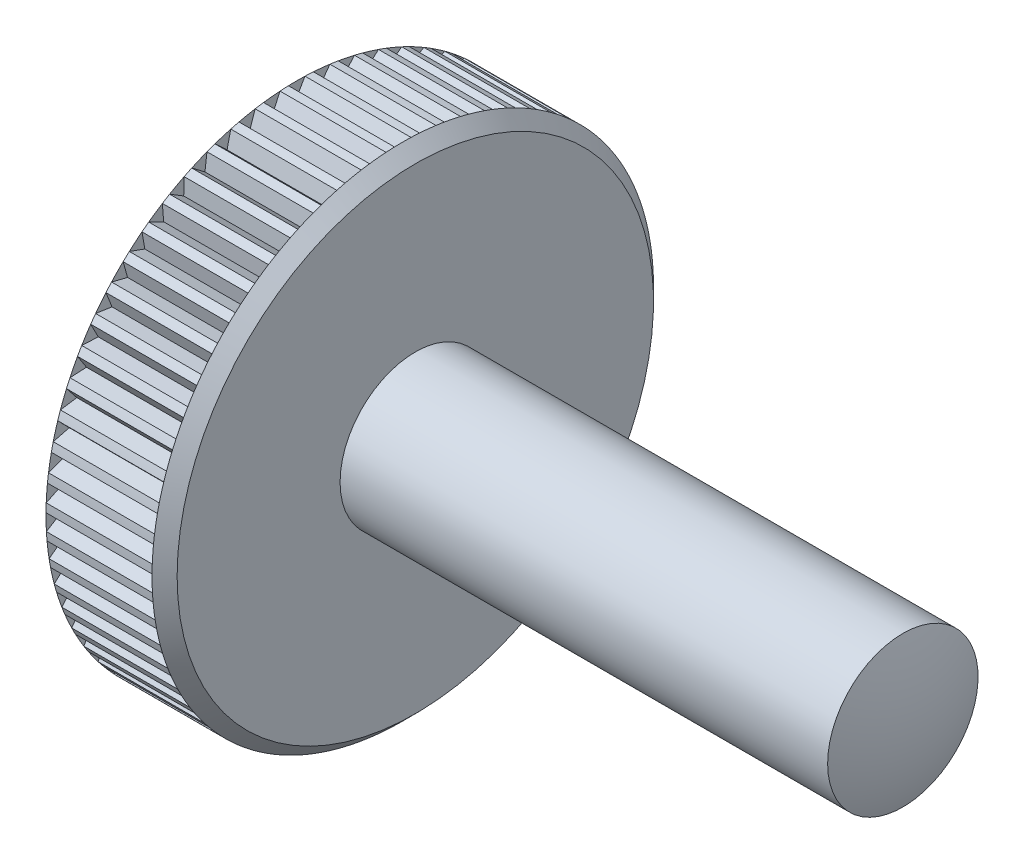
SolidWorks part; units mm, degrees
ref_plane "Front" through (0, 0, 0) normal (0, 0, 1) x (1, 0, 0)
ref_plane "Top" through (0, 0, 0) normal (0, 1, 0) x (1, 0, 0)
ref_plane "Right" through (0, 0, 0) normal (1, 0, 0) x (0, 0, -1)
sketch "Sketch1" plane through (0, 0, 0) normal (0, 0, 1) x (1, 0, 0)
  line L0 (0, 0) -> (26, 0)
  line L1 (1.2702, 10) -> (6, 10)
  line L2 (6, 10) -> (6, 3)
  line L7 (6, 3) -> (25.446, 3)
  line L9 (-48.2111, 0) -> (101.1311, 0) construction
  arc A0 (26, 0) -> (25.446, 3) centre (17.6, 0) ccw
  arc A1 (1.2702, 10) -> (0, 0) centre (40, 0) ccw
  dimension "l" = 20
  dimension "k" = 6
revolve "Base" add sketch "Sketch1" angle 360 about L9
cosmetic thread "ThreadCosmetic1" [suppressed] parameters "THD_MINOR"=4.5
chamfer "Chamfer1" distance 0.5 angle 45 1 edges at (6, 0, 10)
ref_plane "Plane2" through (1.27, 0, 0) normal (1, 0, 0) x (0, 0, -1)
ref_plane "Plane3" through (5.5, 0, 0) normal (1, 0, 0) x (0, 0, -1)
sketch "Sketch2" plane through (1.27, 0, 0) normal (1, 0, 0) x (0, 0, -1)
  line L1 (0, 9.4226) -> (0.5, 10.2887)
  line L2 (0.5, 10.2887) -> (-0.5, 10.2887)
  line L3 (-0.5, 10.2887) -> (0, 9.4226)
  circle A0 centre (0, 0) radius 10 construction
  circle A2 centre (0, 10) radius 0.2887 construction
  dimension "D1" = 1
extrude "Cut-Extrude1" cut sketch "Sketch2" along normal up to surface (4.23 mm away) up to plane "Plane3"
pattern_circular "Circular-Pattern1" count 63 over 360 about axis through (-48.2111, 0, 0) along (1, 0, 0) of "Cut-Extrude1"
sketch "Sketch3" plane through (0, 0, 0) normal (0, 0, 1) x (1, 0, 0)
  line L0 (6, 3.75) -> (6.75, 3.75)
  line L1 (6.75, 3.75) -> (6.75, 3)
  line L2 (6.75, 3) -> (6.375, 2.3505)
  line L3 (6.375, 2.3505) -> (6, 3)
  line L4 (6, 3) -> (6, 3.75)
  line L5 (6, -3) -> (6, 3) construction
  line L6 (25.446, 3) -> (6, 3) construction
  dimension "D1" = 0.75
revolve "Cut-Revolve10" [suppressed] cut sketch "Sketch3" angle 360 about axis through (-48.2111, 0, 0) along (1, 0, 0)
pattern_linear "LPattern10" [suppressed] count 22 along (1, 0, 0) of bodies 104
equation "\"D1@Circular-Pattern1\" =int (  \"dk@Sketch1\" * PI+1 ) "
equation "\"D1@Plane3\" = \"c@Chamfer1\""
equation "\"D1@Sketch3\" =  ( \"d@Sketch1\" - \"THD_MINOR@ThreadCosmetic1\" )  / 2"
equation "\"pitch@LPattern10\" = 1.2 * \"D1@Sketch3\""
equation "\"D1@LPattern10\" = \"l@Sketch1\" / \"pitch@LPattern10\""
